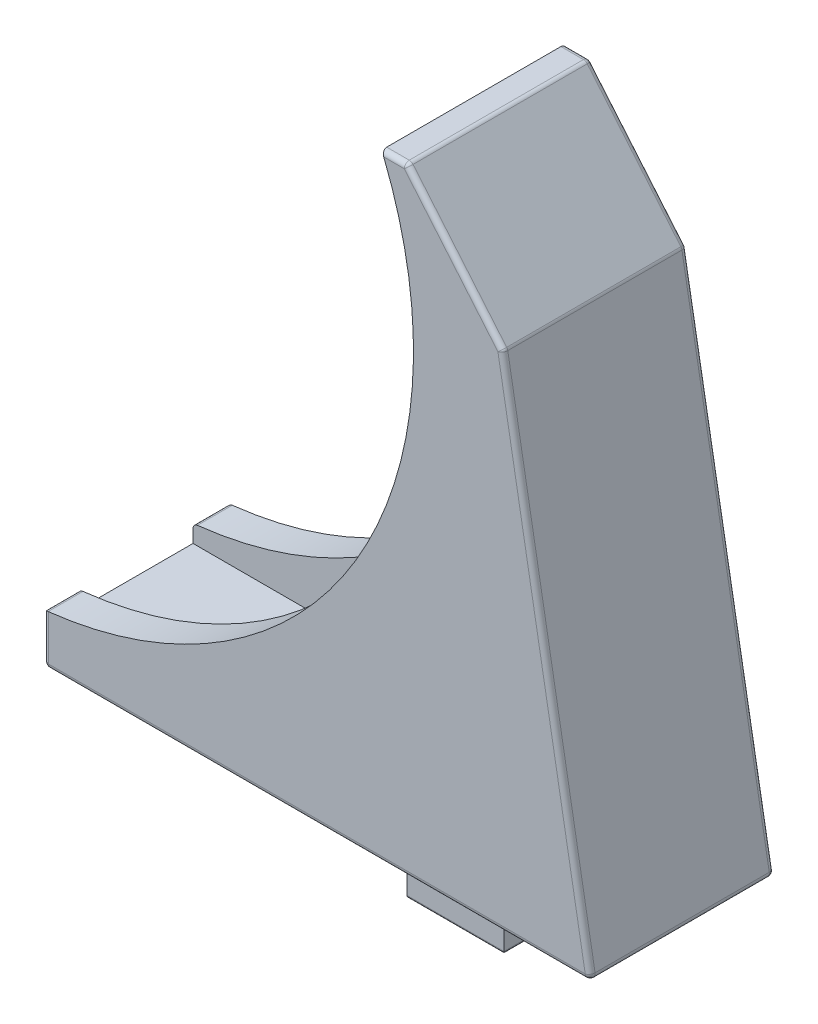
SolidWorks part; units mm, degrees
ref_plane "前视基准面" through (0, 0, 0) normal (0, 0, 1) x (1, 0, 0)
ref_plane "上视基准面" through (0, 0, 0) normal (0, 1, 0) x (1, 0, 0)
ref_plane "右视基准面" through (0, 0, 0) normal (1, 0, 0) x (0, 0, -1)
sketch "草图1" plane through (0, 0, 0) normal (0, 0, 1) x (1, 0, 0)
  line L0 (0, 0) -> (-14.8, 0)
  line L1 (0, 0) -> (7.2, 0)
  line L2 (7.2, 0) -> (3.6402, 20.1886)
  line L3 (3.6402, 20.1886) -> (-0.2165, 24.7848)
  line L4 (-0.2165, 24.7848) -> (-1.2165, 24.7848)
  line L5 (0, 1.3) -> (-14.8, 1.3)
  line L6 (0, 1.3) -> (5.6507, 1.3)
  line L7 (5.6507, 1.3) -> (2.4204, 19.6198)
  line L8 (2.4204, 19.6198) -> (-0.8227, 23.4848)
  line L9 (-0.8227, 23.4848) -> (-1.2165, 23.4848)
  line L10 (-1.2165, 24.7848) -> (-1.2165, 23.4848)
  line L11 (-14.8, 1.3) -> (-14.8, 0)
  dimension "D1" = 7.2
  dimension "D2" = 80
  dimension "D3" = 20.5
  dimension "D4" = 150
  dimension "D5" = 6
  dimension "D6" = 1
  dimension "D7" = 14.8
  dimension "D8" = 1.3
extrude "凸台-拉伸1" add sketch "草图1" along normal blind 2.3 and the other way blind 2.3
sketch "草图2" plane through (0, 0, 2.3) normal (0, 0, 1) x (1, 0, 0)
  line L0 (-14.8, 0) -> (7.2, 0)
  line L1 (7.2, 0) -> (3.6402, 20.1886)
  line L2 (3.6402, 20.1886) -> (-0.2165, 24.7848)
  line L3 (-0.2165, 24.7848) -> (-1.2165, 24.7848)
  line L4 (0, 0) -> (0, 17) construction
  line L5 (-14.8, 0) -> (-14.8, 2)
  arc A0 (-14.8, 2) -> (-1.2165, 24.7848) centre (-16.4391, 18.4186) ccw
  dimension "D1" = 17
  dimension "D2" = 2
extrude "凸台-拉伸2" add sketch "草图2" along normal blind 1.4
mirror "镜向1" about plane through (0, 0, 0) normal (0, 0, 1) of "凸台-拉伸2"
sketch "草图4" plane through (0, 0, 0) normal (0, 0, 1) x (1, 0, 0)
  line L0 (0, 0) -> (0, -2) construction
  line L1 (0, -2) -> (0, -2.5) construction
  line L2 (-1.5, 0) -> (1.5, 0)
  line L3 (-14.8, 0) -> (7.2, 0) construction
  line L4 (1.5, 0) -> (1.5, -0.6771)
  line L5 (-1.95, -2.5) -> (1.95, -2.5)
  line L6 (1.95, -2.5) -> (1.95, -1.5556)
  line L7 (-1.95, -2.5) -> (-1.95, -1.5556)
  line L8 (-1.5, 0) -> (-1.5, -0.6771)
  arc A0 (1.95, -1.5556) -> (1.5, -0.6771) centre (0, -2) ccw
  arc A1 (-1.95, -1.5556) -> (-1.5, -0.6771) centre (0, -2) cw
  dimension "D1" = 2
  dimension "D2" = 0.5
  dimension "D3" = 1.5
  dimension "D4" = 1.95
extrude "凸台-拉伸3" add sketch "草图4" along normal blind 2 and the other way blind 2
sketch "草图5" plane through (0, 0, 3.7) normal (0, 0, 1) x (1, 0, 0)
  line L0 (-1.2165, 24.7848) -> (-14.8, 2)
  arc A0 (-14.8, 2) -> (-1.2165, 24.7848) centre (-16.4391, 18.4186) ccw construction
  arc A1 (-14.8, 2) -> (-1.2165, 24.7848) centre (-16.4391, 18.4186) ccw
extrude "切除-拉伸2" cut sketch "草图5" against normal blind 7.4
sketch "草图6" plane through (0, 0, 0) normal (1, 0, 0) x (0, 0, -1)
  line L0 (0, 0) -> (0, -2) construction
  line L1 (0, -2) -> (0, -2.5) construction
  line L2 (2, -2.5) -> (-2, -2.5) construction
  line L3 (0, 0) -> (1.5, 0) construction
  line L4 (3.7, 0) -> (-3.7, 0) construction
  line L5 (1.5, 0) -> (1.5, -0.6771)
  line L6 (0, -2.5) -> (1.95, -2.5) construction
  line L7 (1.95, -2.5) -> (1.95, -1.5556)
  line L8 (1.95, -2.5) -> (2, -2.5)
  line L9 (2, -2.5) -> (2, 0)
  line L10 (2, 0) -> (1.5, 0)
  line L11 (-1.95, -2.5) -> (-2, -2.5)
  line L12 (-1.95, -2.5) -> (-1.95, -1.5556)
  line L13 (-2, -2.5) -> (-2, 0)
  line L14 (-1.5, 0) -> (-1.5, -0.6771)
  line L15 (-2, 0) -> (-1.5, 0)
  arc A0 (1.95, -1.5556) -> (1.5, -0.6771) centre (0, -2) ccw
  arc A1 (-1.95, -1.5556) -> (-1.5, -0.6771) centre (0, -2) cw
  dimension "D1" = 2
  dimension "D2" = 1.5
  dimension "D3" = 1.95
extrude "切除-拉伸3" cut sketch "草图6" against normal blind 2 and the other way blind 2
fillet "圆角1" radius 0.2 16 edges at (-14.8, 2, -3) (-14.8, 2, 3) (-14.8, 1, 3.7) (-14.8, 1, -3.7) (-0.7165, 24.7848, -3.7) (-0.7165, 24.7848, 3.7) (-0.2165, 24.7848, 0) (1.7118, 22.4867, -3.7) (1.7118, 22.4867, 3.7) (3.6402, 20.1886, 0) (5.4201, 10.0943, -3.7) (5.4201, 10.0943, 3.7) (7.2, 0, 0) (-3.8, 0, -3.7) (-3.8, 0, 3.7) (-14.8, 0, 0)
fillet "圆角2" radius 0.1 4 edges at (0, -2.5, -1.95) (-1.95, -2.5, 0) (0, -2.5, 1.95) (1.95, -2.5, 0)
